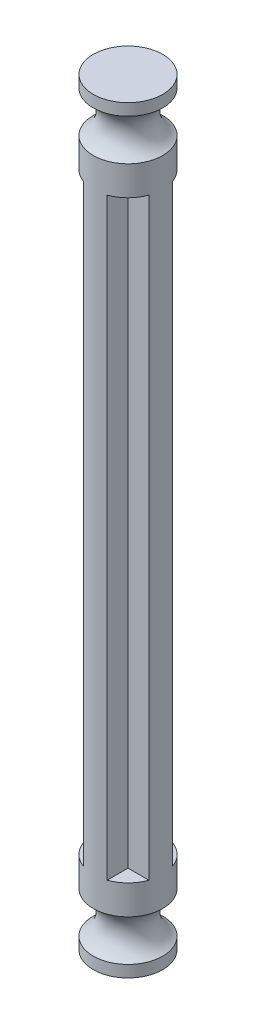
SolidWorks part; units mm, degrees
ref_plane "前视基准面" through (0, 0, 0) normal (0, 0, 1) x (1, 0, 0)
ref_plane "上视基准面" through (0, 0, 0) normal (0, 1, 0) x (1, 0, 0)
ref_plane "右视基准面" through (0, 0, 0) normal (1, 0, 0) x (0, 0, -1)
sketch "草图1" plane through (0, 0, 0) normal (0, 1, 0) x (1, 0, 0)
  line L0 (1, 1) -> (1, 2.7753)
  line L7 (1, 1) -> (2.7753, 1)
  line L8 (1, -1) -> (2.7753, -1)
  line L9 (1, -1) -> (1, -2.7753)
  line L10 (-1, -1) -> (-1, -2.7753)
  line L11 (-1, -1) -> (-2.7753, -1)
  line L12 (-1, 1) -> (-2.7753, 1)
  line L13 (-1, 1) -> (-1, 2.7753)
  arc A0 (-2.7753, 1) -> (-2.7753, -1) centre (0, 0) ccw
  arc A1 (-1, -2.7753) -> (1, -2.7753) centre (0, 0) ccw
  arc A2 (2.7753, -1) -> (2.7753, 1) centre (0, 0) ccw
  arc A3 (1, 2.7753) -> (-1, 2.7753) centre (0, 0) ccw
  dimension "D1" = 5.9
  dimension "D2" = 2
  dimension "D3" = 2
  dimension "D4" = 2
  dimension "D5" = 2
  dimension "D6" = 1
  dimension "D7" = 1
  dimension "D8" = 1
  dimension "D9" = 1
extrude "凸台-拉伸2" add sketch "草图1" along normal blind 50.42
sketch "草图3" plane through (0, 0, 0) normal (1, 0, 0) x (0, 0, -1)
  line L0 (0, 50.42) -> (0, 57.42)
  line L1 (1, 50.42) -> (-1, 50.42) construction
  line L2 (0, 57.42) -> (2.95, 57.42)
  line L3 (0, 50.42) -> (2.95, 50.42)
  line L4 (2.95, 50.42) -> (2.95, 52.92)
  line L5 (2.95, 57.42) -> (2.95, 56.42)
  line L6 (0, 0) -> (0, -7)
  line L7 (0, -7) -> (2.95, -7)
  line L8 (0, 0) -> (2.95, 0)
  line L9 (2.95, 0) -> (2.95, -2.5)
  line L10 (2.95, -7) -> (2.95, -6)
  arc A0 (2.95, 56.42) -> (2.95, 52.92) centre (3.9182, 54.67) ccw
  arc A1 (2.95, -2.5) -> (2.95, -6) centre (3.9182, -4.25) ccw
  dimension "D5" = 1
  dimension "D4" = 2
  dimension "D9" = 2
  dimension "D1" = 2.95
  dimension "D2" = 7
  dimension "D3" = 2.5
  dimension "D6" = 7
  dimension "D7" = 2.5
  dimension "D8" = 1
revolve "旋转3" add sketch "草图3" angle 360 about L6
